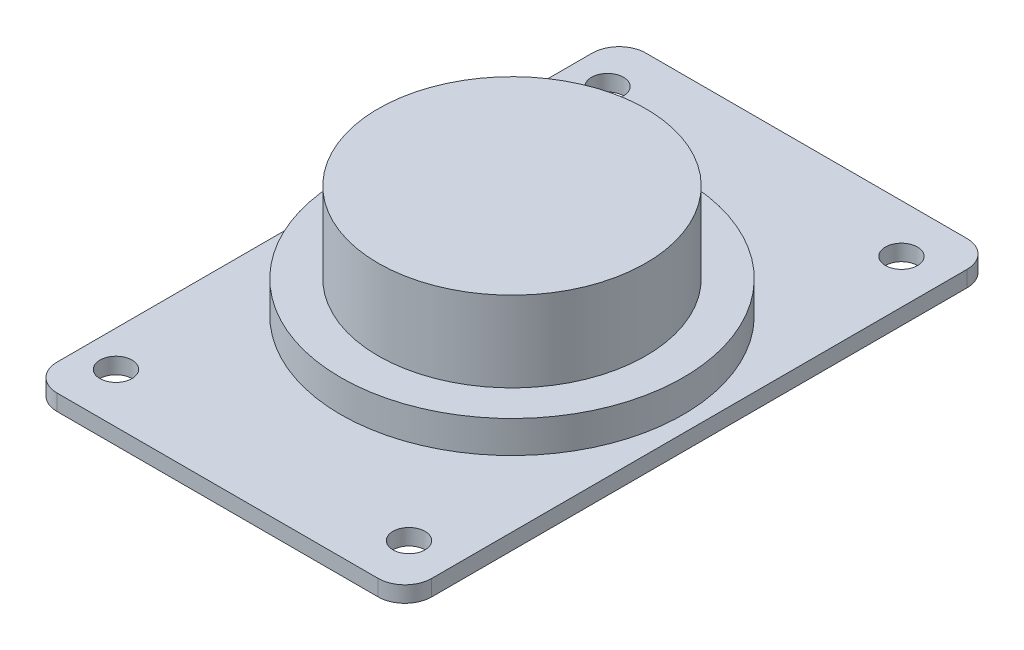
SolidWorks part; units mm, degrees
ref_plane "Front Plane" through (0, 0, 0) normal (0, 0, 1) x (1, 0, 0)
ref_plane "Top Plane" through (0, 0, 0) normal (0, 1, 0) x (1, 0, 0)
ref_plane "Right Plane" through (0, 0, 0) normal (1, 0, 0) x (0, 0, -1)
sketch "Sketch3" plane through (0, 0, 0) normal (0, 1, 0) x (1, 0, 0)
  circle A0 centre (0, 0) radius 25
extrude "Boss-Extrude1" add sketch "Sketch3" against normal blind 15 contours A0
sketch "Sketch4" plane through (0, -15, 0) normal (0, -1, 0) x (1, 0, 0)
  circle A0 centre (0, 0) radius 32
extrude "Boss-Extrude2" add sketch "Sketch4" along normal blind 6
sketch "Sketch6" plane through (0, -21, 0) normal (0, -1, 0) x (1, 0, 0)
  line L1 (35, 0) -> (35, -55)
  line L2 (35, -55) -> (-35, -55)
  line L3 (-35, -55) -> (-35, 55)
  line L4 (-35, 55) -> (35, 55)
  line L5 (35, 55) -> (35, 0)
extrude "Boss-Extrude3" add sketch "Sketch6" along normal blind 3
fillet "Fillet1" radius 5 1 edges at (35, -22.5, 55)
fillet "Fillet2" radius 5 3 edges at (-35, -22.5, 55) (-35, -22.5, -55) (35, -22.5, -55)
sketch "Sketch8" plane through (0, -24, 0) normal (0, -1, 0) x (1, 0, 0)
  circle A0 centre (26.7585, -46) radius 3
  circle A1 centre (-28.159, -46) radius 3
  circle A2 centre (26.7585, 46) radius 3
  circle A3 centre (-28.3209, 45.6631) radius 3
  point P4 (-27.0874, -46)
  point P6 (25.7271, 46)
extrude "Cut-Extrude1" cut sketch "Sketch8" against normal blind 3 contours A3 | A2 | A1 | A0
